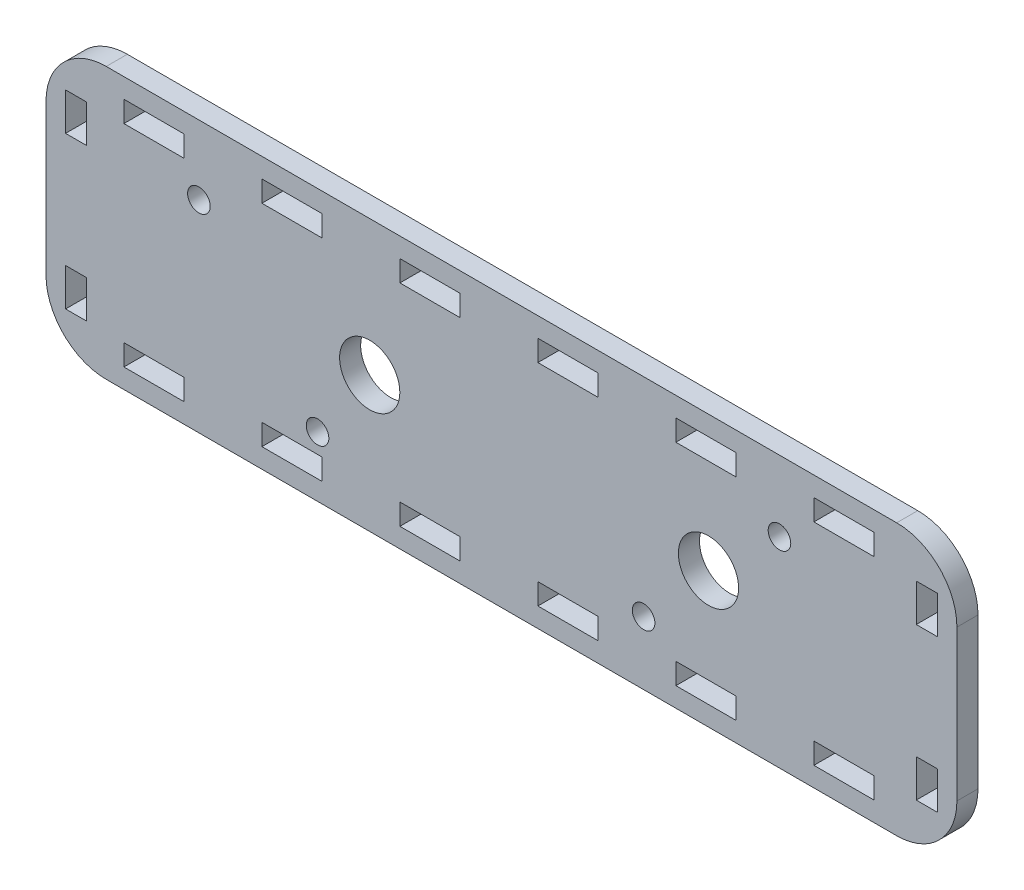
SolidWorks part; units mm, degrees
material "Фанера"
ref_plane "Front Plane" through (0, 0, 0) normal (0, 0, 1) x (1, 0, 0)
ref_plane "Top Plane" through (0, 0, 0) normal (0, 1, 0) x (1, 0, 0)
ref_plane "Right Plane" through (0, 0, 0) normal (1, 0, 0) x (0, 0, -1)
sketch "Эскиз1" plane through (0, 0, 0) normal (0, 0, 1) x (1, 0, 0)
  line L0 (-54.2706, 0) -> (97.4768, 0) construction
  line L1 (-60.5, -18) -> (60.5, -18)
  line L2 (-60.5, -18) -> (-60.5, 18)
  line L3 (-60.5, 18) -> (60.5, 18)
  line L4 (60.5, -18) -> (60.5, 18)
  line L5 (-60.5, -18) -> (60.5, 18) construction
  line L6 (-60.5, 18) -> (60.5, -18) construction
  line L7 (0, 34.2014) -> (0, 18) construction
  line L8 (-56.037, 14) -> (-60.5, 14) construction
  line L10 (41.5, 12.6) -> (49.5, 12.6)
  line L11 (41.5, 12.6) -> (41.5, 15.4)
  line L12 (41.5, 15.4) -> (49.5, 15.4)
  line L13 (49.5, 12.6) -> (49.5, 15.4)
  line L14 (41.5, 12.6) -> (49.5, 15.4) construction
  line L15 (41.5, 15.4) -> (49.5, 12.6) construction
  line L51 (56.5, 24.6844) -> (56.5, 16.8099) construction
  line L53 (55.1, -12.6) -> (57.9, -12.6)
  line L54 (55.1, -12.6) -> (55.1, -7.6)
  line L55 (55.1, -7.6) -> (57.9, -7.6)
  line L56 (57.9, -12.6) -> (57.9, -7.6)
  line L57 (55.1, -12.6) -> (57.9, -7.6) construction
  line L58 (55.1, -7.6) -> (57.9, -12.6) construction
  line L70 (-60, 40.993) -> (-60, -7.3926) construction
  line L71 (-44.6, 14) -> (63.2735, 14) construction
  line L72 (56.5, 0) -> (56.5, -21.7713) construction
  line L73 (55.1, 7.6) -> (57.9, 7.6)
  line L74 (57.9, 12.6) -> (57.9, 7.6)
  line L75 (55.1, 12.6) -> (57.9, 12.6)
  line L76 (55.1, 12.6) -> (55.1, 7.6)
  line L77 (-55.1, -7.6) -> (-57.9, -7.6)
  line L78 (-57.9, -12.6) -> (-57.9, -7.6)
  line L79 (-55.1, -12.6) -> (-57.9, -12.6)
  line L80 (-55.1, -12.6) -> (-55.1, -7.6)
  line L81 (-55.1, 12.6) -> (-55.1, 7.6)
  line L82 (-55.1, 12.6) -> (-57.9, 12.6)
  line L83 (-57.9, 12.6) -> (-57.9, 7.6)
  line L84 (-55.1, 7.6) -> (-57.9, 7.6)
  line L90 (0, 14) -> (0, -27.7796) construction
  line L106 (23.17, 12.6) -> (23.17, 15.4)
  line L107 (23.17, 12.6) -> (31.17, 12.6)
  line L108 (31.17, 12.6) -> (31.17, 15.4)
  line L109 (23.17, 15.4) -> (31.17, 15.4)
  line L110 (4.84, 12.6) -> (4.84, 15.4)
  line L111 (4.84, 12.6) -> (12.84, 12.6)
  line L112 (12.84, 12.6) -> (12.84, 15.4)
  line L113 (4.84, 15.4) -> (12.84, 15.4)
  line L114 (-13.49, 12.6) -> (-13.49, 15.4)
  line L115 (-13.49, 12.6) -> (-5.49, 12.6)
  line L116 (-5.49, 12.6) -> (-5.49, 15.4)
  line L117 (-13.49, 15.4) -> (-5.49, 15.4)
  line L118 (-31.82, 12.6) -> (-31.82, 15.4)
  line L119 (-31.82, 12.6) -> (-23.82, 12.6)
  line L120 (-23.82, 12.6) -> (-23.82, 15.4)
  line L121 (-31.82, 15.4) -> (-23.82, 15.4)
  line L122 (-50.15, 12.6) -> (-50.15, 15.4)
  line L123 (-50.15, 12.6) -> (-42.15, 12.6)
  line L124 (-42.15, 12.6) -> (-42.15, 15.4)
  line L125 (-50.15, 15.4) -> (-42.15, 15.4)
  line L126 (41.5, -15.4) -> (49.5, -15.4)
  line L127 (49.5, -12.6) -> (49.5, -15.4)
  line L128 (41.5, -12.6) -> (49.5, -12.6)
  line L129 (41.5, -12.6) -> (41.5, -15.4)
  line L130 (23.17, -12.6) -> (31.17, -12.6)
  line L131 (31.17, -12.6) -> (31.17, -15.4)
  line L132 (23.17, -15.4) -> (31.17, -15.4)
  line L133 (23.17, -12.6) -> (23.17, -15.4)
  line L134 (4.84, -12.6) -> (12.84, -12.6)
  line L135 (12.84, -12.6) -> (12.84, -15.4)
  line L136 (4.84, -15.4) -> (12.84, -15.4)
  line L137 (4.84, -12.6) -> (4.84, -15.4)
  line L138 (-13.49, -12.6) -> (-5.49, -12.6)
  line L139 (-5.49, -12.6) -> (-5.49, -15.4)
  line L140 (-13.49, -15.4) -> (-5.49, -15.4)
  line L141 (-13.49, -12.6) -> (-13.49, -15.4)
  line L142 (-31.82, -12.6) -> (-23.82, -12.6)
  line L143 (-23.82, -12.6) -> (-23.82, -15.4)
  line L144 (-31.82, -15.4) -> (-23.82, -15.4)
  line L145 (-31.82, -12.6) -> (-31.82, -15.4)
  line L146 (-50.15, -12.6) -> (-42.15, -12.6)
  line L147 (-42.15, -12.6) -> (-42.15, -15.4)
  line L148 (-50.15, -15.4) -> (-42.15, -15.4)
  line L149 (-50.15, -12.6) -> (-50.15, -15.4)
  circle A0 centre (-17.5, 0) radius 4
  circle A1 centre (27.5, 0) radius 4
  circle A2 centre (-5, 0) radius 4
  circle A3 centre (49, 0) radius 4
  point P0 (0, 0)
  point P16 (45.5, 14)
  point P59 (56.5, -10.1)
  point P96 (56.5, -12.6)
  dimension "D2" = 8
  dimension "D1" = 121
  dimension "D3" = 45
  dimension "D4" = 36
  dimension "D5" = 4
  dimension "D6" = 2.8
  dimension "D7" = 8
  dimension "D8" = 15
  dimension "D10" = 4
  dimension "D11" = 2.8
  dimension "D12" = 5
  dimension "D13" = 54
  dimension "D14" = 42.5
  dimension "D15" = 55
  dimension "D16" = 43
  dimension "D17" = 11.5
  dimension "D18" = 6.1
  dimension "D19" = 21.5
  dimension "D20" = 5.4
  dimension "D21" = 50.1
  dimension "D9" = 6
extrude "Бобышка-Вытянуть1" add sketch "Эскиз1" along normal mid plane 2.8 contours L1 L4 L3 L2 A3 A2 A1 A0 L73 L56 L53 L54 L55 L136 L138 L134 L126 L133 L132 L131 L130 L128 | A3 | A2 region at (-0.6859, 0, 0) region at (-5, 0, 0) region at (49, 0, 0)
sketch "Эскиз2" plane through (0, 0, 1.4) normal (0, 0, 1) x (1, 0, 0)
  line L4 (-60.5, -18) -> (60.5, -18)
  line L5 (60.5, -18) -> (60.5, 18)
  line L6 (60.5, 18) -> (-60.5, 18)
  line L7 (-60.5, 18) -> (-60.5, -18)
  line L8 (-60.5, -18) -> (60.5, -18)
  line L9 (60.5, -18) -> (60.5, 18)
  line L10 (60.5, 18) -> (-60.5, 18)
  line L11 (-60.5, 18) -> (-60.5, -18)
  circle A0 centre (-40.1886, 8.8) radius 1.5 construction
  circle A1 centre (-24.4311, -10) radius 1.5 construction
  circle A2 centre (18.8807, -9.6) radius 1.5 construction
  circle A3 centre (36.9288, 8.6) radius 1.5 construction
  circle A4 centre (-40.1886, 8.8) radius 1.5
  circle A5 centre (-24.4311, -10) radius 1.5
  circle A6 centre (18.8807, -9.6) radius 1.5
  circle A7 centre (36.9288, 8.6) radius 1.5
  dimension "D1" = 0
extrude "Вырез-Вытянуть1" cut sketch "Эскиз2" against normal through all both and the other way through all contours A4 | A5 | A6 | A7 region at (-40.1886, 8.8, 1.4) region at (-24.4311, -10, 1.4) region at (18.8807, -9.6, 1.4) region at (36.9288, 8.6, 1.4)
fillet "Скругление1" radius 8 4 edges at (60.5, -18, 0) (60.5, 18, 0) (-60.5, -18, 0) (-60.5, 18, 0)
equation "\"D14@Эскиз1\"=170*0.25"
